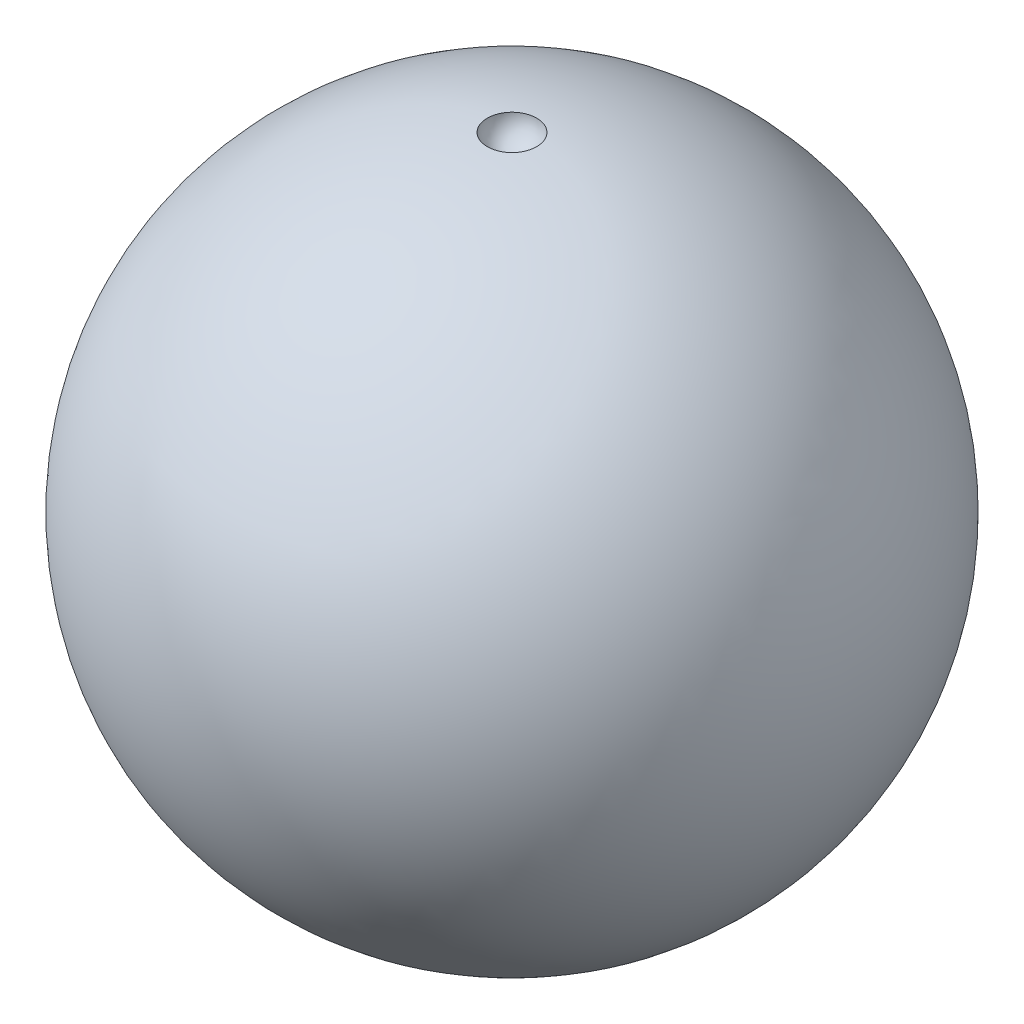
SolidWorks part; units mm, degrees
ref_plane "Front Plane" through (0, 0, 0) normal (0, 0, 1) x (1, 0, 0)
ref_plane "Top Plane" through (0, 0, 0) normal (0, 1, 0) x (1, 0, 0)
ref_plane "Right Plane" through (0, 0, 0) normal (1, 0, 0) x (0, 0, -1)
sketch "Sketch1" plane through (0, 0, 0) normal (0, 0, 1) x (1, 0, 0)
  line L0 (0, 20) -> (0, 0)
  line L1 (0, 0) -> (20, 0)
  arc A0 (20, 0) -> (0, 20) centre (0, 0) ccw
  dimension "D1" = 20
revolve "Revolve1" add sketch "Sketch1" angle 360 about L0
sketch "Sketch3" plane through (0, 0, 0) normal (0, 0, 1) x (1, 0, 0)
  line L0 (0, 0) -> (0, 20) construction
  line L1 (0, 18.5) -> (1.5802, 18.5) construction
  line L2 (0, 18.5) -> (0, 20)
  arc A0 (20, 0) -> (-20, 0) centre (0, 0) ccw construction
  arc A1 (0, 20) -> (-1.5, 19.9437) centre (0, 0) ccw
  arc A2 (-1.5, 19.9437) -> (0, 18.5) centre (0, 20.0011) ccw
  dimension "D1" = 1.5
  dimension "D2" = 1.5
revolve "Cut-Revolve1" cut sketch "Sketch3" angle 360 about L2 region at (-0.6291, 19.3534, 0)
ref_axis "Axis1" through (-23.485, 0, 0) along (1, 0, 0)
ref_axis "Axis2" through (0, 22.2927, 0) along (0, -1, 0)
ref_axis "Axis3" through (0, 0, -23.485) along (0, 0, 1)
mirror "Mirror1" about plane through (0, 0, 0) normal (0, 1, 0) of bodies 103 115
